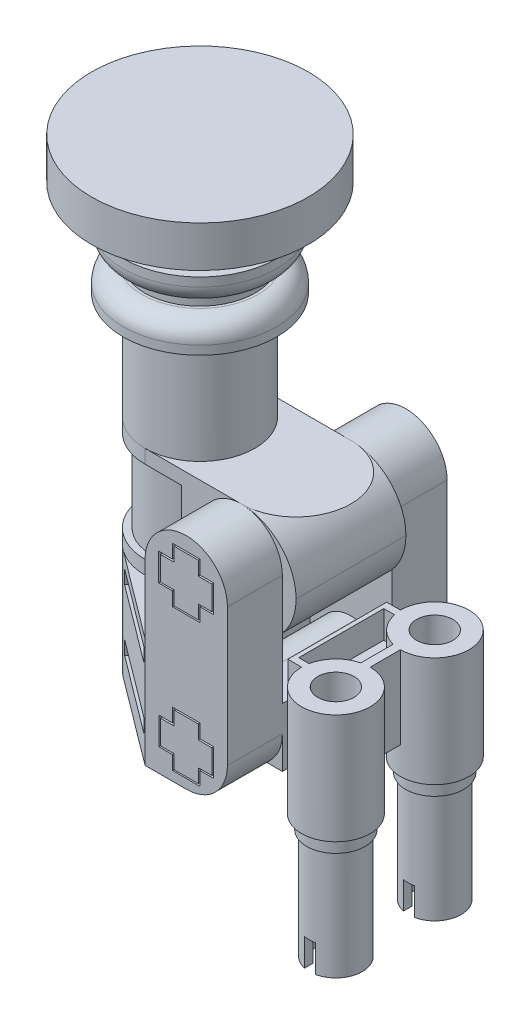
SolidWorks part; units mm, degrees
ref_plane "Front Plane" through (0, 0, 0) normal (0, 0, 1) x (1, 0, 0)
ref_plane "Top Plane" through (0, 0, 0) normal (0, 1, 0) x (1, 0, 0)
ref_plane "Right Plane" through (0, 0, 0) normal (1, 0, 0) x (0, 0, -1)
sketch "Sketch1" plane through (0, 0, 0) normal (0, 1, 0) x (1, 0, 0)
  line L0 (0, 0) -> (-7, 0) construction
  line L1 (0, -4) -> (-7, -4)
  line L2 (0, 4) -> (-7, 4)
  arc A0 (0, -4) -> (0, 4) centre (0, 0) ccw
  arc A1 (-7, 4) -> (-7, -4) centre (-7, 0) ccw
  point P3 (-3.5, 0)
  point P8 (-11, 0)
  point P9 (4, 0)
  dimension "D1" = 15
  dimension "D2" = 4
extrude "Boss-Extrude1" add sketch "Sketch1" along normal blind 0.0001
sketch "Sketch18" plane through (0, 0, 0) normal (0, -1, 0) x (1, 0, 0)
  line L0 (-7, 4) -> (4, 4)
  line L1 (4, 4) -> (4, -4)
  line L2 (4, -4) -> (-7, -4)
  arc A0 (-7, 4) -> (-7, -4) centre (-7, 0) ccw
extrude "Boss-Extrude2" add sketch "Sketch18" along normal blind 8 separate body
fillet "Fillet1" radius 4 1 edges at (4, -8, 0)
fillet "Fillet2" radius 4 1 edges at (4, 0, 0)
sketch "Sketch19" plane through (0, -8, 0) normal (0, -1, 0) x (1, 0, 0)
  line L0 (-2.2158, 0.3807) -> (0, 0.3807)
  line L1 (0, -4) -> (0, 4) construction
  line L2 (0, 0.3807) -> (0, -0.6611)
  line L3 (0, -0.6611) -> (-2.2465, -0.6611)
  arc A0 (-2.2158, 0.3807) -> (-2.2465, -0.6611) centre (-7, 0) ccw
  circle A1 centre (-7, 0) radius 3.5
extrude "Cut-Extrude1" cut sketch "Sketch19" against normal blind 6 from offset 1 offset against normal yes
sketch "Sketch20" plane through (0, -8, 0) normal (0, -1, 0) x (1, 0, 0)
  line L0 (-11, 0) -> (-3, 0) construction
  line L1 (-9.4, 3.2) -> (-3, 8)
  line L2 (-3, 4) -> (-3, -4)
  line L3 (-3, 0) -> (-9.4, 0)
  line L4 (-9.4, -3.2) -> (-9.4, 3.2)
  line L5 (-9.4, -3.2) -> (-3, -8)
  line L6 (-3, 8) -> (-3, -8)
  arc A0 (-7, 4) -> (-7, -4) centre (-7, 0) ccw construction
  dimension "D1" = 16
  dimension "D2" = 8
  dimension "D7" = 6.4
extrude "Boss-Extrude3" add sketch "Sketch20" along normal blind 8 separate body
sketch "Sketch22" plane through (0, 0, -4) normal (0, 0, -1) x (-1, 0, 0)
  line L0 (0, -3) -> (0, -13) construction
  line L1 (3, -3) -> (3, -13)
  line L2 (-3, -3) -> (-3, -13)
  arc A0 (3, -3) -> (-3, -3) centre (0, -3) ccw
  arc A1 (-3, -13) -> (3, -13) centre (0, -13) ccw
  point P2 (0, -8)
  point P7 (0, 0)
  point P8 (0, -16)
  dimension "D1" = 16
  dimension "D2" = 6
extrude "Boss-Extrude4" add sketch "Sketch22" along normal blind 4 separate body
sketch "Sketch23" plane through (0, 0, 4) normal (0, 0, 1) x (1, 0, 0)
  line L0 (0, -3) -> (0, -13) construction
  line L1 (3, -3) -> (3, -13)
  line L2 (-3, -3) -> (-3, -13)
  arc A0 (3, -3) -> (-3, -3) centre (0, -3) ccw
  arc A1 (-3, -13) -> (3, -13) centre (0, -13) ccw
  point P2 (0, -8)
  dimension "D2" = 6
extrude "Boss-Extrude11" add sketch "Sketch23" along normal blind 4 separate body
sketch "Sketch25" plane through (0, 0, 8) normal (0, 0, 1) x (1, 0, 0)
  line L0 (0, -16) -> (-3, -16)
  line L1 (-3, -13) -> (-3, -16)
  line L2 (-3, -16) -> (-3, -8) construction
  arc A0 (-3, -13) -> (3, -13) centre (0, -13) ccw construction
  arc A1 (-3, -13) -> (0, -16) centre (0, -13) ccw
extrude "Boss-Extrude12" add sketch "Sketch25" against normal blind 4
sketch "Sketch26" plane through (0, 0, -8) normal (0, 0, -1) x (-1, 0, 0)
  line L0 (3, -13) -> (3, -16)
  line L1 (3, -16) -> (0, -16)
  arc A0 (0, -16) -> (3, -13) centre (0, -13) ccw
  arc A1 (-3, -13) -> (3, -13) centre (0, -13) ccw construction
extrude "Boss-Extrude13" add sketch "Sketch26" against normal blind 4
sketch "Sketch27" plane through (0, 0, -8) normal (0, 0, -1) x (-1, 0, 0)
  line L1 (-1, -1.5) -> (1, -1.5)
  line L2 (-1, -1.5) -> (-1, -2.5)
  line L3 (-1, -5.5) -> (1, -5.5)
  line L4 (1, -1.5) -> (1, -2.5)
  line L6 (-0.875, -2.6341) -> (-1.875, -2.6341)
  line L7 (2, -2.5) -> (1, -2.5)
  line L8 (2, -2.5) -> (2, -4.5)
  line L9 (2, -4.5) -> (1, -4.5)
  line L10 (-2, -2.5) -> (-2, -4.5)
  line L11 (1.875, -4.3841) -> (0.875, -4.3841)
  line L16 (1.875, -4.3841) -> (1.875, -2.6341)
  line L17 (1.875, -2.6341) -> (0.875, -2.6341)
  line L21 (-1.875, -4.3841) -> (-1.875, -2.6341)
  line L24 (-1, -2.5) -> (-2, -2.5)
  line L26 (-1, -4.5) -> (-1, -5.5)
  line L28 (1, -4.5) -> (1, -5.5)
  line L29 (-1, -4.5) -> (-2, -4.5)
  line L30 (0.875, -5.3932) -> (-0.875, -5.3932)
  line L31 (0.875, -5.3932) -> (0.875, -4.3841)
  line L32 (0.875, -1.625) -> (-0.875, -1.625)
  line L34 (-0.875, -5.3932) -> (-0.875, -4.3841)
  line L38 (-0.875, -2.6341) -> (-0.875, -1.625)
  line L41 (-0.875, -4.3841) -> (-1.875, -4.3841)
  line L42 (0.875, -2.6341) -> (0.875, -1.625)
  line L43 (-1, -11.3645) -> (1, -11.3645)
  line L44 (-1, -11.3645) -> (-1, -12.3645)
  line L45 (-1, -15.3645) -> (1, -15.3645)
  line L46 (1, -11.3645) -> (1, -12.3645)
  line L47 (-0.875, -12.4986) -> (-1.875, -12.4986)
  line L48 (2, -12.3645) -> (1, -12.3645)
  line L49 (2, -12.3645) -> (2, -14.3645)
  line L50 (2, -14.3645) -> (1, -14.3645)
  line L51 (-2, -12.3645) -> (-2, -14.3645)
  line L52 (1.875, -14.2486) -> (0.875, -14.2486)
  line L53 (1.875, -14.2486) -> (1.875, -12.4986)
  line L54 (1.875, -12.4986) -> (0.875, -12.4986)
  line L55 (-1.875, -14.2486) -> (-1.875, -12.4986)
  line L56 (-1, -12.3645) -> (-2, -12.3645)
  line L57 (-1, -14.3645) -> (-1, -15.3645)
  line L58 (1, -14.3645) -> (1, -15.3645)
  line L59 (-1, -14.3645) -> (-2, -14.3645)
  line L60 (0.875, -15.2577) -> (-0.875, -15.2577)
  line L61 (0.875, -15.2577) -> (0.875, -14.2486)
  line L62 (0.875, -11.4895) -> (-0.875, -11.4895)
  line L63 (-0.875, -15.2577) -> (-0.875, -14.2486)
  line L64 (-0.875, -12.4986) -> (-0.875, -11.4895)
  line L65 (-0.875, -14.2486) -> (-1.875, -14.2486)
  line L66 (0.875, -12.4986) -> (0.875, -11.4895)
  point P0 (0, -3.5091)
  point P5 (0, -3.5091)
  point P12 (0, -13.3736)
  point P17 (0, -13.3736)
  point P25 (0, -1.5)
  point P29 (0, -3.5091)
  point P31 (0, -11.3645)
  point P36 (0, -3.5091)
  point P45 (0, -13.3736)
  point P51 (0, -13.3736)
  point P60 (0, -11.4895)
  point P61 (-1.875, -13.3736)
  point P62 (0, -1.625)
  point P64 (-1.875, -3.5091)
  dimension "D1" = 2
  dimension "D2" = 4
  dimension "D3" = 2
  dimension "D4" = 4
  dimension "D5" = 2
  dimension "D6" = 4
  dimension "D7" = 2
  dimension "D8" = 4
  dimension "D9" = 1.75
  dimension "D10" = 3.75
  dimension "D11" = 1.75
  dimension "D12" = 1.75
  dimension "D13" = 3.75
  dimension "D14" = 1.75
extrude "Cut-Extrude3" cut sketch "Sketch27" against normal blind 2
sketch "Sketch30" plane through (0, 0, 8) normal (0, 0, 1) x (1, 0, 0)
  line L0 (-1, -0.9886) -> (1, -0.9886)
  line L1 (-1, -0.9886) -> (-1, -1.9886)
  line L2 (-1, -4.9886) -> (1, -4.9886)
  line L3 (1, -0.9886) -> (1, -1.9886)
  line L4 (-0.875, -2.1227) -> (-1.875, -2.1227)
  line L5 (1.9975, -1.9886) -> (1, -1.9886)
  line L6 (1.9975, -1.9886) -> (1.9975, -3.9886)
  line L7 (1.9975, -3.9886) -> (1, -3.9886)
  line L8 (-2.0025, -1.9886) -> (-2.0025, -3.9886)
  line L9 (1.875, -3.8727) -> (0.875, -3.8727)
  line L10 (1.875, -3.8727) -> (1.875, -2.1227)
  line L11 (1.875, -2.1227) -> (0.875, -2.1227)
  line L12 (-1.875, -3.8727) -> (-1.875, -2.1227)
  line L13 (-1, -1.9886) -> (-2.0025, -1.9886)
  line L14 (-1, -3.9886) -> (-1, -4.9886)
  line L15 (1, -3.9886) -> (1, -4.9886)
  line L16 (-1, -3.9886) -> (-2.0025, -3.9886)
  line L17 (0.875, -4.8818) -> (-0.875, -4.8818)
  line L18 (0.875, -4.8818) -> (0.875, -3.8727)
  line L19 (0.875, -1.1136) -> (-0.875, -1.1136)
  line L20 (-0.875, -4.8818) -> (-0.875, -3.8727)
  line L21 (-0.875, -2.1227) -> (-0.875, -1.1136)
  line L22 (-0.875, -3.8727) -> (-1.875, -3.8727)
  line L23 (0.875, -2.1227) -> (0.875, -1.1136)
  line L24 (-1, -11.3203) -> (1, -11.3203)
  line L25 (-1, -11.3203) -> (-1, -12.3203)
  line L26 (-1, -15.3203) -> (1, -15.3203)
  line L27 (1, -11.3203) -> (1, -12.3203)
  line L28 (-0.875, -12.4544) -> (-1.875, -12.4544)
  line L29 (2, -12.3203) -> (1, -12.3203)
  line L30 (2, -12.3203) -> (2, -14.3203)
  line L31 (2, -14.3203) -> (1, -14.3203)
  line L32 (-2, -12.3203) -> (-2, -14.3203)
  line L33 (1.875, -14.2044) -> (0.875, -14.2044)
  line L34 (1.875, -14.2044) -> (1.875, -12.4544)
  line L35 (1.875, -12.4544) -> (0.875, -12.4544)
  line L36 (-1.875, -14.2044) -> (-1.875, -12.4544)
  line L37 (-1, -12.3203) -> (-2, -12.3203)
  line L38 (-1, -14.3203) -> (-1, -15.3203)
  line L39 (1, -14.3203) -> (1, -15.3203)
  line L40 (-1, -14.3203) -> (-2, -14.3203)
  line L41 (0.875, -15.2135) -> (-0.875, -15.2135)
  line L42 (0.875, -15.2135) -> (0.875, -14.2044)
  line L43 (0.875, -11.4453) -> (-0.875, -11.4453)
  line L44 (-0.875, -15.2135) -> (-0.875, -14.2044)
  line L45 (-0.875, -12.4544) -> (-0.875, -11.4453)
  line L46 (-0.875, -14.2044) -> (-1.875, -14.2044)
  line L47 (0.875, -12.4544) -> (0.875, -11.4453)
  point P0 (0, -2.9977)
  point P5 (-0.0025, -2.9977)
  point P12 (0, -0.9886)
  point P15 (0, -2.9977)
  point P20 (0, -2.9977)
  point P29 (0, -1.1136)
  point P30 (-1.875, -2.9977)
  point P34 (0, -13.3294)
  point P39 (0, -13.3294)
  point P46 (0, -11.3203)
  point P49 (0, -13.3294)
  point P54 (0, -13.3294)
  point P63 (0, -11.4453)
  point P64 (-1.875, -13.3294)
  dimension "D1" = 2
  dimension "D2" = 4
  dimension "D3" = 2
  dimension "D4" = 4
  dimension "D5" = 1.75
  dimension "D6" = 3.75
  dimension "D7" = 1.75
  dimension "D8" = 2
  dimension "D9" = 4
  dimension "D10" = 2
  dimension "D11" = 4
  dimension "D12" = 1.75
  dimension "D13" = 3.75
  dimension "D14" = 1.75
extrude "Cut-Extrude6" cut sketch "Sketch30" against normal blind 2
sketch "Sketch33" plane through (0, 0, 4) normal (0, 0, -1) x (-1, 0, 0)
  circle A0 centre (0, -13.5331) radius 2.4669
extrude "Boss-Extrude14" add sketch "Sketch33" along normal up to body separate body
sketch "Sketch34" plane through (0, -8, 0) normal (0, -1, 0) x (1, 0, 0)
  line L0 (-9.4, -3.2) -> (-9.4, 3.2) construction
  line L1 (-9.4, 3.2) -> (-9.4, -3.2)
  arc A0 (-9.4, 3.2) -> (-9.4, -3.2) centre (-7, 0) ccw
  arc A1 (-7, 4) -> (-7, -4) centre (-7, 0) ccw construction
extrude "Boss-Extrude16" add sketch "Sketch34" along normal blind 8 separate body
sketch "Sketch35" plane through (3, 0, 0) normal (1, 0, 0) x (0, 0, -1)
  line L0 (-4, -13) -> (-4, -3) construction
  line L1 (-4, -11.0948) -> (4, -11.0948)
  line L2 (-4, -11.0948) -> (-4, -15.3826)
  line L3 (-4, -15.3826) -> (4, -15.3826)
  line L4 (4, -11.0948) -> (4, -15.3826)
  line L5 (4, -16) -> (4, -11.0662) construction
extrude "Boss-Extrude17" add sketch "Sketch35" against normal up to body separate body
ref_plane "Plane1" through (0, -8.5, 0) normal (0, 1, 0) x (1, 0, 0)
sketch "Sketch36" plane through (0, -8.5, 0) normal (0, 1, 0) x (1, 0, 0)
  line L0 (3, 0) -> (0.8069, 0) construction
  line L1 (3, 3.6) -> (4, 3.6)
  line L2 (3, 3.6) -> (3, -3.6)
  line L3 (3, -3.6) -> (4, -3.6)
  line L4 (4, 3.6) -> (4, -3.6)
  line L5 (3, 4) -> (3, -4) construction
  point P9 (3, 0)
  dimension "D1" = 7.2
  dimension "D2" = 1
extrude "Boss-Extrude18" add sketch "Sketch36" against normal blind 6
sketch "Sketch37" plane through (0, -8.5, 0) normal (0, 1, 0) x (1, 0, 0)
  circle A0 centre (6.4999, 3.6) radius 2.4999
  circle A1 centre (6.4999, -3.6) radius 2.4999
  dimension "D1" = 2
  dimension "D2" = 4.9998
extrude "Boss-Extrude19" add sketch "Sketch37" against normal blind 8 separate body
sketch "Sketch38" plane through (0, -8.5, 0) normal (0, 1, 0) x (1, 0, 0)
  line L0 (4, -3.6) -> (4, 3.6) construction
  line L1 (4, 3.6) -> (4, -3.6)
  line L2 (6.4999, 1.1001) -> (6.4999, -1.1001)
  arc A0 (4, 3.6) -> (6.4999, 1.1001) centre (6.4999, 3.6) ccw
  circle A1 centre (6.4999, 3.6) radius 2.4999 construction
  arc A2 (4, -3.6) -> (6.4999, -1.1001) centre (6.4999, -3.6) cw
  circle A3 centre (6.4999, -3.6) radius 2.4999 construction
extrude "Boss-Extrude20" add sketch "Sketch38" against normal blind 6
sketch "Sketch39" plane through (0, -8.5, 0) normal (0, 1, 0) x (1, 0, 0)
  line L0 (3.2985, 3.0896) -> (4.0884, 3.0896)
  line L1 (3.2985, 3.0896) -> (3.2985, -3.1041)
  line L2 (3.2985, -3.1041) -> (4.0497, -3.1041)
  line L3 (5.8895, 1.1757) -> (5.8895, -1.1758)
  line L4 (3, 3.6) -> (3, -3.6) construction
  arc A2 (4.0884, 3.0896) -> (5.8895, 1.1757) centre (6.5377, 3.5901) ccw
  arc A3 (5.8895, -1.1758) -> (4.0497, -3.1041) centre (6.4999, -3.6) ccw
  dimension "D1" = 2.4999
  dimension "D2" = 0.2985
  dimension "D3" = 1.0497
  dimension "D4" = 1.0884
  dimension "D5" = 2.8895
  dimension "D6" = 3.5377
  dimension "D7" = 4.7757
extrude "Cut-Extrude7" cut sketch "Sketch39" against normal blind 2
sketch "Sketch40" plane through (0, -16.5, 0) normal (0, -1, 0) x (1, 0, 0)
  circle A1 centre (6.4999, 3.6) radius 2.123
  circle A2 centre (6.4999, -3.6) radius 2.123
  circle A3 centre (6.4999, 3.6) radius 2.4999 construction
  dimension "D2" = 4.246
  dimension "D3" = 7.2
  dimension "D1" = 2
extrude "Boss-Extrude21" add sketch "Sketch40" along normal blind 1 separate body
sketch "Sketch41" plane through (0, -17.5, 0) normal (0, -1, 0) x (1, 0, 0)
  circle A0 centre (6.4999, 3.6) radius 1.923
  circle A1 centre (6.4999, 3.6) radius 1.323
  circle A2 centre (6.4999, -3.6) radius 1.923
  circle A3 centre (6.4999, -3.6) radius 1.323
  circle A4 centre (6.4999, 3.6) radius 2.123 construction
  dimension "D3" = 2.646
  dimension "D4" = 7.2
  dimension "D1" = 0.6
  dimension "D2" = 2
extrude "Boss-Extrude22" add sketch "Sketch41" along normal blind 8 separate body
sketch "Sketch42" plane through (0, -25.5, 0) normal (0, -1, 0) x (1, 0, 0)
  circle A0 centre (6.4999, 3.6) radius 1.323
  circle A1 centre (6.4999, -3.6) radius 1.325
  dimension "D1" = 2.646
  dimension "D2" = 2.65
extrude "Cut-Extrude9" cut sketch "Sketch42" against normal blind 18 contours A0 | A1
sketch "Sketch44" plane through (0, -25.5, 0) normal (0, -1, 0) x (1, 0, 0)
  line L0 (6.0999, 5.6008) -> (6.0999, 1.6008)
  line L3 (6.8999, 5.5992) -> (6.8999, 1.6008)
  line L4 (6.0999, -1.5992) -> (6.0999, -5.5992)
  line L5 (6.8999, -1.6008) -> (6.8999, -5.5992)
  line L6 (6.8999, 5.5992) -> (6.0999, 1.6008) construction
  line L7 (6.0999, 5.6008) -> (6.8999, 1.6008) construction
  arc A2 (6.0999, 1.6008) -> (6.8999, 1.6008) centre (6.4999, 3.4962) ccw
  arc A3 (6.0999, 5.6008) -> (6.8999, 5.5992) centre (6.4962, 3.7045) cw
  circle A4 centre (6.4999, 3.6) radius 1.923 construction
  arc A5 (6.0999, -5.5992) -> (6.8999, -5.5992) centre (6.4999, -3.7038) ccw
  arc A6 (6.0999, -1.5992) -> (6.8999, -1.6008) centre (6.4962, -3.4955) cw
  point P6 (6.4999, 3.6)
  point P7 (6.4999, 1.559)
  point P19 (6.4999, 4.923)
  point P21 (5.1769, 3.6)
  dimension "D2" = 0.8
  dimension "D4" = 1.9372
  dimension "D1" = 2
  dimension "D3" = 4
  dimension "D5" = 7.2
  dimension "D6" = 0.0037
extrude "Cut-Extrude12" cut sketch "Sketch44" against normal blind 2
sketch "Sketch47" plane through (-4.92, 0, -6.56) normal (-0.6, 0, -0.8) x (-0.8, 0, 0.6)
  line L0 (-2.4, -16) -> (-2.4, -8) construction
  line L1 (-1.9429, -8.8072) -> (5.0319, -8.8072)
  line L2 (-1.9429, -8.8072) -> (-1.9429, -9.8072)
  line L3 (-1.9429, -9.8072) -> (5.0319, -9.8072)
  line L4 (5.0319, -8.8072) -> (5.0319, -9.8072)
  line L5 (-1.9429, -13.273) -> (5.0319, -13.273)
  line L6 (-1.9429, -13.273) -> (-1.9429, -14.273)
  line L7 (-1.9429, -14.273) -> (5.0319, -14.273)
  line L8 (5.0319, -13.273) -> (5.0319, -14.273)
  line L9 (5.6, -8) -> (-2.4, -8) construction
  dimension "D1" = 1
  dimension "D2" = 0.4571
  dimension "D3" = 7.4319
  dimension "D4" = 0.8072
  dimension "D5" = 5.273
extrude "Cut-Extrude15" cut sketch "Sketch47" against normal blind 1
mirror "Mirror2" about plane through (0, 0, 0) normal (0, 0, 1) of "Cut-Extrude15"
sketch "Sketch48" plane through (0, 0.0001, 0) normal (0, 1, 0) x (1, 0, 0)
  circle A0 centre (-7, 0) radius 4
  arc A1 (-7, 4) -> (-7, -4) centre (-7, 0) ccw construction
extrude "Boss-Extrude23" add sketch "Sketch48" along normal blind 7.82
sketch "Sketch49" plane through (0, 7.8201, 0) normal (0, 1, 0) x (1, 0, 0)
  circle A0 centre (-7, 0) radius 5.59
  dimension "D1" = 11.18
extrude "Boss-Extrude24" add sketch "Sketch49" along normal blind 2
fillet "Fillet3" radius 1.36 1 edges at (-7, 9.8201, 5.59)
sketch "Sketch50" plane through (0, 9.8201, 0) normal (0, 1, 0) x (1, 0, 0)
  circle A0 centre (-7, 0) radius 4.035
  dimension "D1" = 8.07
extrude "Boss-Extrude25" add sketch "Sketch50" along normal blind 0.94
sketch "Sketch51" plane through (0, 10.7601, 0) normal (0, 1, 0) x (1, 0, 0)
  circle A0 centre (-7, 0) radius 5.59
  dimension "D1" = 11.18
extrude "Boss-Extrude26" add sketch "Sketch51" along normal blind 2 contours A0
fillet "Fillet4" radius 1.36 1 edges at (-7, 10.7601, 5.59)
sketch "Sketch52" plane through (0, 12.7601, 0) normal (0, 1, 0) x (1, 0, 0)
  circle A0 centre (-7, 0) radius 2.115
  dimension "D1" = 4.23
extrude "Boss-Extrude28" add sketch "Sketch52" along normal blind 2.04
sketch "Sketch53" plane through (0, 14.8001, 0) normal (0, 1, 0) x (1, 0, 0)
  circle A0 centre (-7, 0) radius 7.895
  dimension "D1" = 15.79
extrude "Boss-Extrude29" add sketch "Sketch53" along normal blind 3
